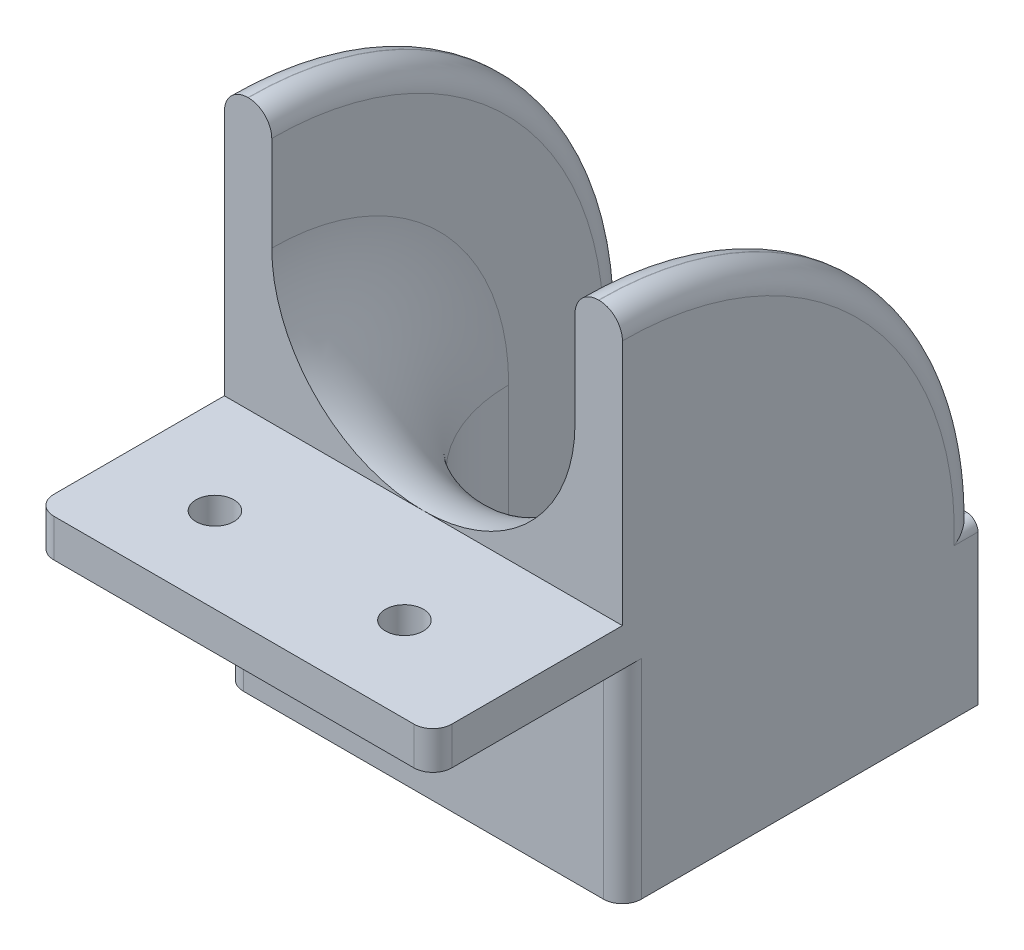
SolidWorks part; units mm, degrees
ref_plane "Front Plane" through (0, 0, 0) normal (0, 0, 1) x (1, 0, 0)
ref_plane "Top Plane" through (0, 0, 0) normal (0, 1, 0) x (1, 0, 0)
ref_plane "Right Plane" through (0, 0, 0) normal (1, 0, 0) x (0, 0, -1)
sketch "Sketch1" plane through (0, 0, 0) normal (0, 1, 0) x (1, 0, 0)
  line L0 (0, 0) -> (40.64, 0)
  line L3 (0, 31.75) -> (-6.35, 31.75)
  line L4 (0, 31.75) -> (0, 0)
  line L5 (0, 0) -> (-6.35, 0)
  line L6 (-6.35, 31.75) -> (-6.35, 0)
  line L7 (40.64, 31.75) -> (46.99, 31.75)
  line L8 (40.64, 31.75) -> (40.64, 0)
  line L9 (40.64, 0) -> (46.99, 0)
  line L10 (46.99, 31.75) -> (46.99, 0)
  line L11 (-6.35, 31.75) -> (0, 31.75)
  line L12 (-6.35, 31.75) -> (-6.35, 44.4754)
  line L13 (-3.2004, 47.625) -> (-3.1496, 47.625)
  line L14 (0, 31.75) -> (0, 44.4754)
  line L15 (46.99, 31.75) -> (40.64, 31.75)
  line L16 (46.99, 31.75) -> (46.99, 44.4754)
  line L17 (43.8404, 47.625) -> (43.7896, 47.625)
  line L18 (40.64, 31.75) -> (40.64, 44.4754)
  arc A0 (0, 31.75) -> (40.64, 31.75) centre (20.32, 31.75) ccw
  arc A1 (46.99, 44.4754) -> (43.8404, 47.625) centre (43.8404, 44.4754) ccw
  arc A2 (43.7896, 47.625) -> (40.64, 44.4754) centre (43.7896, 44.4754) ccw
  arc A3 (-3.1496, 47.625) -> (0, 44.4754) centre (-3.1496, 44.4754) cw
  arc A4 (-6.35, 44.4754) -> (-3.2004, 47.625) centre (-3.2004, 44.4754) cw
  point P16 (46.99, 47.625)
  dimension "D5" = 3.1496
  dimension "D1" = 40.64
  dimension "D2" = 31.75
  dimension "D3" = 6.35
  dimension "D4" = 15.875
revolve "Revolve1" add sketch "Sketch1" angle 90 about L0 region at (20.32, 0, -8.5467) region at (-3.175, 0, -15.875) region at (43.815, 0, -15.875) region at (-3.175, 0, -39.3685) region at (43.815, 0, -39.3685)
sketch "Sketch2" plane through (0, 0, 0) normal (0, -1, 0) x (1, 0, 0)
  line L7 (43.7896, -47.625) -> (43.8404, -47.625)
  line L8 (46.99, -44.4754) -> (46.99, 0)
  line L9 (46.99, 0) -> (-6.35, 0)
  line L10 (-6.35, 0) -> (-6.35, -44.4754)
  line L11 (-3.2004, -47.625) -> (-3.1496, -47.625)
  line L12 (0, -44.4754) -> (0, -31.75)
  line L13 (40.64, -31.75) -> (40.64, -44.4754)
  line L14 (43.7896, -47.625) -> (43.8404, -47.625)
  line L15 (46.99, -44.4754) -> (46.99, 0)
  line L16 (46.99, 0) -> (-6.35, 0)
  line L17 (-6.35, 0) -> (-6.35, -44.4754)
  line L18 (-3.2004, -47.625) -> (-3.1496, -47.625)
  line L19 (0, -44.4754) -> (0, -31.75)
  line L20 (40.64, -31.75) -> (40.64, -44.4754)
  arc A5 (43.8404, -47.625) -> (46.99, -44.4754) centre (43.8404, -44.4754) ccw
  arc A6 (-6.35, -44.4754) -> (-3.2004, -47.625) centre (-3.2004, -44.4754) ccw
  arc A7 (-3.1496, -47.625) -> (0, -44.4754) centre (-3.1496, -44.4754) ccw
  arc A8 (40.64, -31.75) -> (0, -31.75) centre (20.32, -31.75) ccw
  arc A9 (40.64, -44.4754) -> (43.7896, -47.625) centre (43.7896, -44.4754) ccw
  arc A10 (43.8404, -47.625) -> (46.99, -44.4754) centre (43.8404, -44.4754) ccw
  arc A11 (-6.35, -44.4754) -> (-3.2004, -47.625) centre (-3.2004, -44.4754) ccw
  arc A12 (-3.1496, -47.625) -> (0, -44.4754) centre (-3.1496, -44.4754) ccw
  arc A13 (40.64, -31.75) -> (0, -31.75) centre (20.32, -31.75) ccw
  arc A14 (40.64, -44.4754) -> (43.7896, -47.625) centre (43.7896, -44.4754) ccw
  dimension "D1" = 0
extrude "Boss-Extrude1" add sketch "Sketch2" along normal blind 21.59
sketch "Sketch9" plane through (0, 0, 0) normal (0, 0, 1) x (1, 0, 0)
  line L0 (-6.35, 44.4754) -> (-6.35, -21.59) construction
  line L1 (-6.35, 11.43) -> (46.99, 11.43)
  line L2 (-6.35, 11.43) -> (-6.35, 6.35)
  line L3 (-6.35, 6.35) -> (46.99, 6.35)
  line L4 (46.99, 11.43) -> (46.99, 6.35)
  line L5 (46.99, -21.59) -> (46.99, 44.4754) construction
  arc A0 (0, 31.75) -> (40.64, 31.75) centre (20.32, 31.75) ccw construction
  dimension "D2" = 20.32
  dimension "D1" = 5.08
extrude "Boss-Extrude7" add sketch "Sketch9" along normal blind 25.4
sketch "Sketch10" plane through (0, 11.43, 0) normal (0, 1, 0) x (1, 0, 0)
  line L1 (20.32, 0) -> (-6.35, 0) construction
  line L2 (-6.35, -25.4) -> (-6.35, 0) construction
  circle A0 centre (6.35, -13.97) radius 2.54
  circle A1 centre (31.75, -13.97) radius 2.54
  dimension "D1" = 5.08
  dimension "D2" = 13.97
  dimension "D3" = 12.7
  dimension "D4" = 25.4
extrude "Cut-Extrude1" cut sketch "Sketch10" against normal through all
fillet "Fillet1" radius 2.54 4 edges at (-6.35, -7.62, 0) (46.99, 8.89, 25.4) (46.99, -7.62, 0) (-6.35, 8.89, 25.4)
sketch "Sketch11" plane through (0, -21.59, 0) normal (0, -1, 0) x (1, 0, 0)
  line L0 (40.64, -31.75) -> (40.64, -44.4754) construction
  line L1 (0, -44.4754) -> (0, -31.75) construction
  line L5 (40.64, -31.75) -> (40.64, -44.4754)
  line L6 (0, -44.4754) -> (0, -31.75)
  line L10 (43.7896, -47.6504) -> (-3.2004, -47.6504)
  line L11 (-3.2004, -47.6504) -> (-3.2004, -41.3004)
  line L12 (-3.2004, -44.4754) -> (43.7896, -44.4754)
  line L13 (43.7896, -41.3004) -> (43.7896, -47.6504)
  line L14 (43.7896, -44.4754) -> (46.99, -44.4754)
  line L15 (46.99, -41.3004) -> (46.99, -47.6504)
  line L16 (46.99, -47.6504) -> (43.7896, -47.6504)
  line L17 (-3.2004, -44.4754) -> (-6.35, -44.4754)
  line L18 (-6.35, -41.3004) -> (-6.35, -47.6504)
  line L19 (-6.35, -47.6504) -> (-3.2004, -47.6504)
  line L20 (-6.35, -41.3004) -> (-3.2004, -41.3004)
  line L21 (46.99, -41.3004) -> (43.7896, -41.3004)
  line L22 (43.7896, -41.3004) -> (-3.2004, -41.3004)
  arc A0 (40.64, -31.75) -> (0, -31.75) centre (20.32, -31.75) ccw construction
  arc A3 (40.64, -31.75) -> (0, -31.75) centre (20.32, -31.75) ccw
  line M9 (-6.35, -2.54) -> (-6.35, -44.4754)
  arc M10 (-6.35, -44.4754) -> (-3.2004, -47.625) centre (-3.2004, -44.4754) ccw
  arc M12 (-3.1496, -47.625) -> (0, -44.4754) centre (-3.1496, -44.4754) ccw
  line M13 (0, -44.4754) -> (0, -31.75)
  arc M16 (40.64, -44.4754) -> (43.7896, -47.625) centre (43.7896, -44.4754) ccw
  line M17 (43.7896, -47.625) -> (43.8404, -47.625)
  arc M18 (43.8404, -47.625) -> (46.99, -44.4754) centre (43.8404, -44.4754) ccw
  line M19 (46.99, -44.4754) -> (46.99, -2.54)
  dimension "D1" = 3.175
extrude "Boss-Extrude8" add sketch "Sketch11" against normal blind 21.59 contours L12 L10 M12 M16 | L16 L15 L13 M18 M17 | L18 L19 L11 M10 | L5 L22 L12 M13 | L21 L13 L14 M19 | L20 L17 L11 M9 region at (20.32, -21.59, -42.8879) region at (19.0737, -21.59, -46.0767) region at (45.3898, -21.59, -42.8879) region at (46.2535, -21.59, -46.9478) region at (-4.7752, -21.59, -42.8879) region at (-5.6149, -21.59, -46.9474)
ref_plane "Plane1" through (20.32, 0, 0) normal (-1, 0, 0) x (0, 0, 1)
fillet "Fillet4" radius 1.524 7 edges at (40.64, -21.59, -36.5252) (20.32, -21.59, -11.43) (0, -21.59, -36.5252) (-6.35, 0, -46.0629) (46.99, 0, -46.0629) (20.32, 0, -41.3004) (20.32, -21.59, -41.3004)
sketch "Sketch15" plane through (20.32, 0, 0) normal (-1, 0, 0) x (0, 0, 1)
  circle A0 centre (-4.9171, 2.9058) radius 277.85
